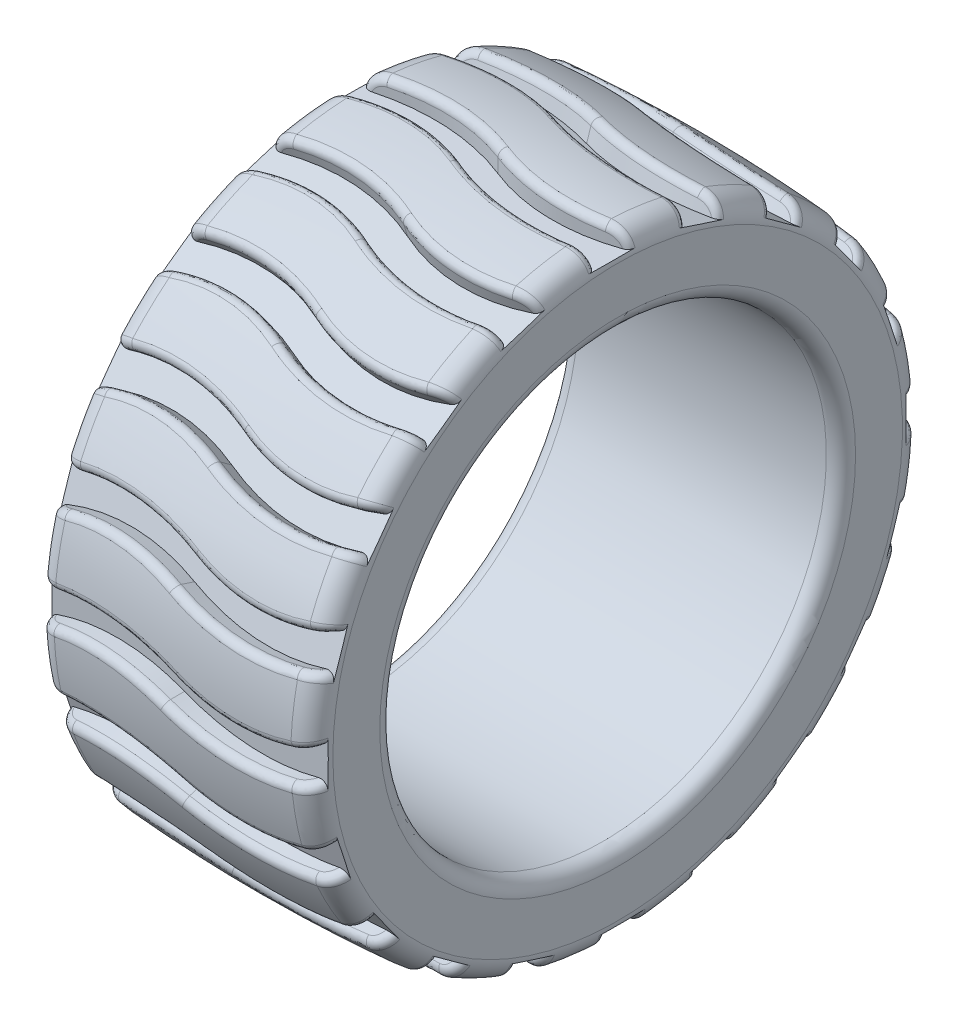
SolidWorks part; units mm, degrees
ref_plane "Plan de face" through (0, 0, 0) normal (0, 0, 1) x (1, 0, 0)
ref_plane "Plan de dessus" through (0, 0, 0) normal (0, 1, 0) x (1, 0, 0)
ref_plane "Plan de droite" through (0, 0, 0) normal (1, 0, 0) x (0, 0, -1)
sketch "Esquisse1" plane through (0, 0, 0) normal (0, 0, 1) x (1, 0, 0)
  line L0 (0, 0) -> (0, 21.3) construction
  line L1 (-9.5, 20.9) -> (-9.5, 15.3)
  line L2 (-9.5, 15.3) -> (9.5, 15.3)
  line L3 (9.5, 15.3) -> (9.5, 20.9)
  arc A0 (-9.5, 20.9) -> (9.5, 20.9) centre (0, -91.7125) cw
  dimension "D1" = 21.3
  dimension "D2" = 20.9
  dimension "D3" = 19
  dimension "D4" = 6
ref_axis "Axe2" through (-10.45, 0, 0) along (1, 0, 0)
revolve "Révolution1" add sketch "Esquisse1" angle 360 about axis through (-10.45, 0, 0) along (1, 0, 0)
fillet "Congé1" radius 1.5 2 edges at (9.5, 0, 20.9) (-9.5, 0, 20.9)
fillet "Congé2" radius 1 2 edges at (-9.5, 0, 15.3) (9.5, 0, 15.3)
sketch "Esquisse3" plane through (0, 0, 0) normal (0, 1, 0) x (1, 0, 0)
  line L0 (-10.45, 0) -> (10.45, 0) construction
  line L1 (0, 0) -> (-10, 0) construction
  line L2 (0, 0) -> (10, 0) construction
  line L3 (-9.629, -0.9286) -> (-10.371, 0.9286)
  line L4 (9.629, 0.9286) -> (10.371, -0.9286)
  arc A0 (-10, 0) -> (0, 0) centre (-5, -12.5145) cw construction
  arc A1 (0, 0) -> (10, 0) centre (5, 12.5145) ccw construction
  arc A2 (-9.629, -0.9286) -> (-0.371, -0.9286) centre (-5, -12.5145) cw
  arc A3 (-0.371, -0.9286) -> (10.371, -0.9286) centre (5, 12.5145) ccw
  arc A4 (-10.371, 0.9286) -> (0.371, 0.9286) centre (-5, -12.5145) cw
  arc A5 (0.371, 0.9286) -> (9.629, 0.9286) centre (5, 12.5145) ccw
  dimension "D1" = 20
  dimension "D2" = 1
  dimension "D3" = 1
extrude "Enlèv. mat.-Extru.1" cut sketch "Esquisse3" against normal blind 1.5 from offset 21.3 contours A4 A5 L4 A3 A2 L3
fillet "Congé3" radius 0.5 8 edges at (9.032, 20.5543, 1.389) (3.2576, 21.1718, 1.8566) (-8.9738, 20.6422, 0.6879) (9.0408, 20.5806, -0.7106) (3.9642, 21.2303, -0.0812) (-8.9663, 20.6119, -1.4079) (-4.4289, 21.2131, 0.0512) (-4.3724, 21.1257, -1.9483)
pattern_circular "Répétition circulaire1" count 20 over 360 about axis through (-10.45, 0, 0) along (1, 0, 0) of "Enlèv. mat.-Extru.1", "Congé3"
